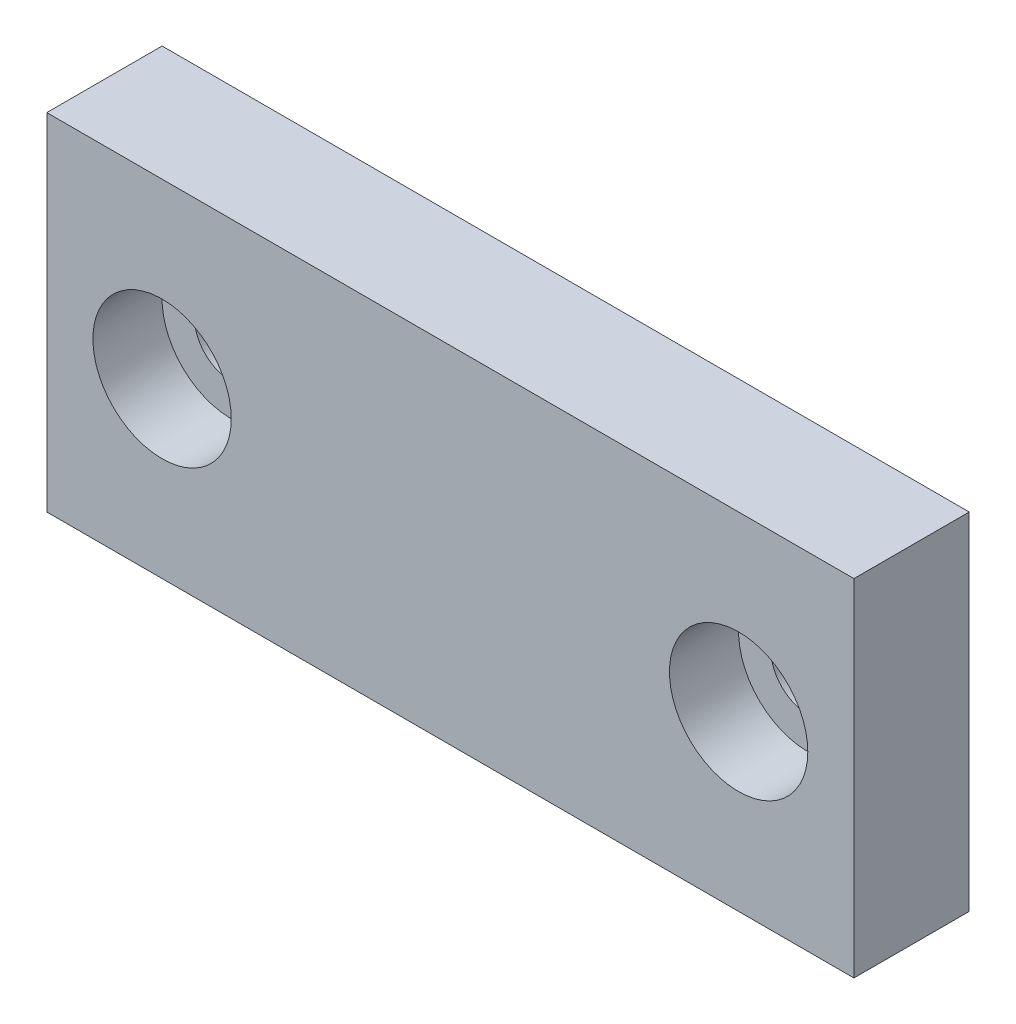
SolidWorks part; units mm, degrees
ref_plane "Front Plane" through (0, 0, 0) normal (0, 0, 1) x (1, 0, 0)
ref_plane "Top Plane" through (0, 0, 0) normal (0, 1, 0) x (1, 0, 0)
ref_plane "Right Plane" through (0, 0, 0) normal (1, 0, 0) x (0, 0, -1)
sketch "Sketch1" plane through (0, 0, 0) normal (0, 0, 1) x (1, 0, 0)
  line L0 (10, 0) -> (10, -30) construction
  line L1 (0, 0) -> (70, 0)
  line L2 (0, 0) -> (0, -30)
  line L3 (0, -30) -> (70, -30)
  line L4 (70, 0) -> (70, -30)
  line L5 (60, 0) -> (60, -30) construction
  dimension "D1" = 70
  dimension "D2" = 30
  dimension "D3" = 10
  dimension "D4" = 10
extrude "Boss-Extrude1" add sketch "Sketch1" along normal blind 10
sketch "Sketch2" plane through (0, 0, 10) normal (0, 0, 1) x (1, 0, 0)
  line L0 (60, 0) -> (60, -30) construction
  line L1 (10, 0) -> (10, -30) construction
  line L2 (60, 0) -> (60, -30)
  line L3 (10, 0) -> (10, -30)
  circle A0 centre (10, -15) radius 6
  circle A1 centre (60, -15) radius 6
  dimension "D1" = 12
  dimension "D2" = 12
extrude "Cut-Extrude1" cut sketch "Sketch2" against normal blind 6 contours A0 | A1
sketch "Sketch3" plane through (0, 0, 4) normal (0, 0, 1) x (1, 0, 0)
  line L0 (10, 0) -> (10, -30) construction
  line L1 (60, 0) -> (60, -30) construction
  circle A0 centre (10, -15) radius 3.2
  circle A1 centre (60, -15) radius 3.2
  dimension "D1" = 6.4
  dimension "D2" = 6.4
extrude "Cut-Extrude2" cut sketch "Sketch3" against normal through all
ref_plane "Plane1" through (0, 0, 0) normal (0, 1, 0) x (1, 0, 0)
sketch "Sketch9" plane through (0, 0, 0) normal (0, 1, 0) x (1, 0, 0)
  line L0 (50, -25.4) -> (50, -10)
  line L1 (70, -10) -> (0, -10) construction
  line L2 (20, -25.4) -> (20, -10)
  line L3 (20, -10) -> (50, -10)
  circle A0 centre (35, -25.4) radius 15
  arc A1 (20, -25.4) -> (50, -25.4) centre (35, -25.4) cw
  point P0 (0, 0)
  dimension "D1" = 30
sketch "Sketch10" plane through (0, 0, 10) normal (0, 0, 1) x (1, 0, 0)
  line L0 (10, -15) -> (60, -15) construction
  line L1 (10, 0) -> (10, -30) construction
  line L2 (60, 0) -> (60, -30) construction
